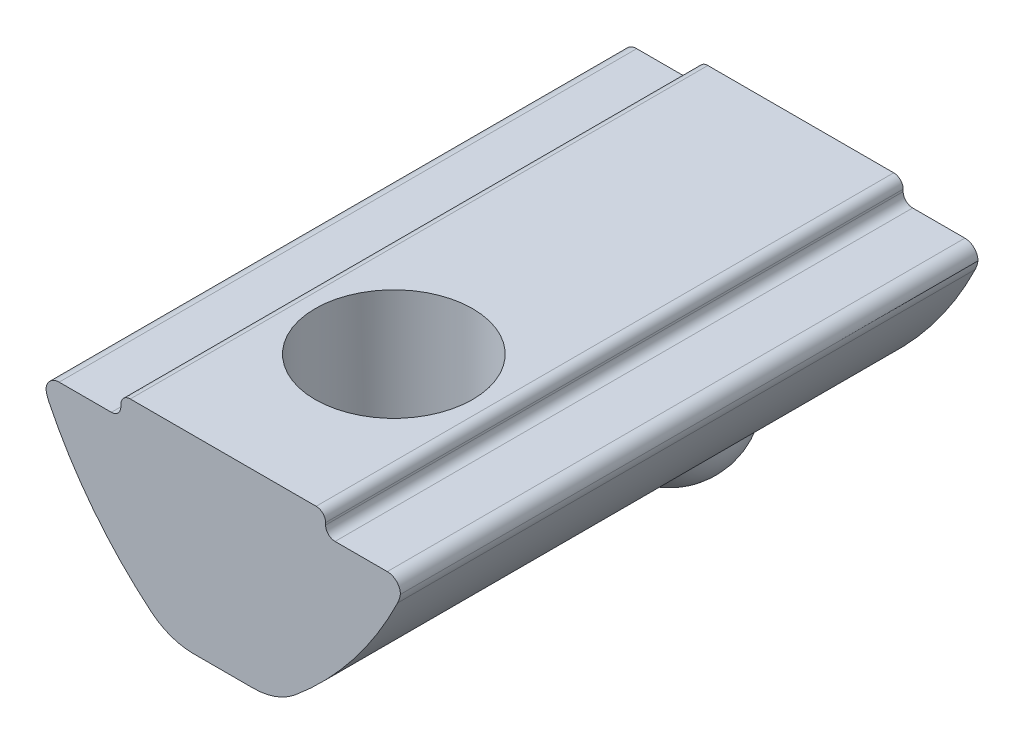
SolidWorks part; units mm, degrees
material "Plain Carbon Steel"
ref_plane "Front Plane" through (0, 0, 0) normal (0, 0, 1) x (1, 0, 0)
ref_plane "Top Plane" through (0, 0, 0) normal (0, 1, 0) x (1, 0, 0)
ref_plane "Right Plane" through (0, 0, 0) normal (1, 0, 0) x (0, 0, -1)
sketch "Sketch1" plane through (0, 0, 0) normal (0, 1, 0) x (1, 0, 0)
  circle A0 centre (0, 0) radius 3
  point P2 (3, 0)
  point P3 (-3, 0)
  dimension "D1" = 6
extrude "Boss-Extrude1" add sketch "Sketch1" against normal blind 16
sketch "Sketch2" plane through (0, -16, 0) normal (0, -1, 0) x (1, 0, 0)
  circle A1 centre (0, 0) radius 3
  circle A2 centre (0, 0) radius 3
  point P0 (0, -3)
  dimension "D1" = 0
curve "Helix/Spiral1" pitch 1 height 17 turns 17
sketch "Sketch3" plane through (0, 0, 0) normal (1, 0, 0) x (0, 0, -1)
  line L0 (3.1083, -15.9375) -> (2.2422, -16.4375) construction
  line L1 (2.2422, -16.4375) -> (3.1083, -16.9375) construction
  line L2 (3.1083, -16.9375) -> (3.1083, -15.9375) construction
  line L3 (2.3505, -16.375) -> (2.3505, -16.5) construction
  line L4 (3, -16) -> (3, -16.875) construction
  line L5 (2.2422, -16.4375) -> (2.3505, -16.4375) construction
  line L6 (3, -16.4375) -> (3.1083, -16.4375) construction
  line L8 (2.2422, -16.4375) -> (-3, -16.4375) construction
  line L9 (2.3505, -16.375) -> (3.0541, -15.9688)
  line L10 (2.3505, -16.375) -> (2.3505, -16.5)
  line L11 (2.3505, -16.5) -> (3.0541, -16.9063)
  line L12 (3.0541, -16.9063) -> (3.0541, -15.9688)
  line L14 (-3, -16.4375) -> (-3, -15.4375) construction
  line L15 (-3, -15.4375) -> (-3, -14.4375) construction
  line L16 (-3, -14.4375) -> (-3, -13.4375) construction
  line L17 (-3, -13.4375) -> (-3, -12.4375) construction
  line L18 (-3, 0) -> (-3, -16) construction
  point P15 (3.0541, -16.4375)
  dimension "D1" = 1
  dimension "D2" = 0.125
sweep "Cut-Sweep1" cut profiles "Sketch3" path "Helix/Spiral1" align with end faces yes
sketch "SketchZ" plane through (0, 0, 0) normal (0, 0, 1) x (1, 0, 0)
  line L0 (0, -16.4375) -> (0, -15.9375) construction
  line L1 (0, -16.1875) -> (3, -16.1875) construction
  line L2 (3, -16.1875) -> (3, -15.1875) construction
  line L3 (0, -16.4375) -> (0, -15.4375) construction
sketch "Sketch4" plane through (0, -16, 0) normal (0, -1, 0) x (1, 0, 0)
  circle A0 centre (0, 0) radius 2.2422
extrude "Cut-Extrude1" cut sketch "Sketch4" against normal blind 1 draft 45 flip side to cut
sketch "Sketch5" plane through (0, 0, 0) normal (0, 0, 1) x (1, 0, 0)
  line L0 (0, 3.3) -> (0, 0)
  line L1 (0, 0) -> (-6.8, 0) construction
  line L2 (0, 3.3) -> (-3, 3.3)
  line L3 (-6.8, 0) -> (-6.8, 0.825) construction
  line L4 (-6.8, 0.825) -> (-5.25, 0.825) construction
  line L5 (0, 0) -> (0, -13.9857) construction
  line L6 (-5.25, 0.825) -> (-5.25, 0)
  line L7 (-5.25, 0) -> (0, 0)
  arc A0 (-5.25, 0.825) -> (-3, 3.3) centre (0, -1.6875) cw
  dimension "D1" = 10.5
  dimension "D2" = 6.8
  dimension "D3" = 3.3
  dimension "D4" = 0.825
revolve "Revolve1" add sketch "Sketch5" angle 360 mid plane about L5
sketch "Sketch6" plane through (0, 3.3, 0) normal (0, 1, 0) x (1, 0, 0)
  line L1 (0, 2.3094) -> (-2, 1.1547)
  line L2 (-2, 1.1547) -> (-2, -1.1547)
  line L3 (-2, -1.1547) -> (0, -2.3094)
  line L4 (0, -2.3094) -> (2, -1.1547)
  line L5 (2, -1.1547) -> (2, 1.1547)
  line L6 (2, 1.1547) -> (0, 2.3094)
  circle A0 centre (0, 0) radius 2 construction
  dimension "D1" = 4
extrude "Cut-Extrude2" cut sketch "Sketch6" against normal blind 2.4
sketch "Sketch7" plane through (0, 3.3, 0) normal (0, 1, 0) x (1, 0, 0)
  circle A0 centre (0, 0) radius 2.3094
extrude "Cut-Extrude3" cut sketch "Sketch7" against normal blind 2.4 draft 45
sketch "Sketch8" plane through (0, 0, 0) normal (0, 0, 1) x (1, 0, 0)
  line L0 (6.75, -8) -> (6.75, -15.2) construction
  line L4 (6.75, -15.2) -> (-6.75, -15.2) construction
  line L7 (-6.75, -8) -> (6.75, -8) construction
  line L10 (0, 0) -> (0, -8) construction
  line L11 (-6.75, -15.2) -> (-6.75, -8) construction
  line L12 (-1.1419, -15.2) -> (1.1419, -15.2)
  line L13 (-3.54, -8) -> (3.54, -8)
  line L14 (-3.9, -8.36) -> (-3.9, -8.44)
  line L15 (-4.26, -8.8) -> (-6.25, -8.8)
  line L16 (3.9, -8.36) -> (3.9, -8.44)
  line L17 (4.26, -8.8) -> (6.25, -8.8)
  line L18 (0, -8) -> (0, -15.2) construction
  arc A1 (-2.741, -14.6217) -> (-6.6417, -9.6394) centre (6.8537, -3.0916) cw
  arc A2 (-3.54, -8) -> (-3.9, -8.36) centre (-3.54, -8.36) ccw
  arc A3 (-3.9, -8.44) -> (-4.26, -8.8) centre (-4.26, -8.44) cw
  arc A4 (-6.25, -8.8) -> (-6.75, -9.3) centre (-6.25, -9.3) ccw
  arc A5 (-6.75, -9.3) -> (-6.6417, -9.6394) centre (-5.5171, -9.0938) ccw
  arc A6 (-1.1419, -15.2) -> (-2.741, -14.6217) centre (-1.1419, -12.7) cw
  arc A7 (3.54, -8) -> (3.9, -8.36) centre (3.54, -8.36) cw
  arc A8 (3.9, -8.44) -> (4.26, -8.8) centre (4.26, -8.44) ccw
  arc A9 (6.25, -8.8) -> (6.75, -9.3) centre (6.25, -9.3) cw
  arc A10 (6.75, -9.3) -> (6.6417, -9.6394) centre (5.5171, -9.0938) cw
  arc A11 (2.741, -14.6217) -> (6.6417, -9.6394) centre (-6.8537, -3.0916) ccw
  arc A12 (1.1419, -15.2) -> (2.741, -14.6217) centre (1.1419, -12.7) ccw
  point P4 (-2, -15.2)
  point P25 (-2, -15.2)
  dimension "D1" = 13.5
  dimension "D3" = 4
  dimension "D4" = 15
  dimension "D6" = 7.8
  dimension "D8" = 0.36
  dimension "D9" = 1.25
  dimension "D10" = 0.5
  dimension "D11" = 2.5
  dimension "D2" = 8
  dimension "D5" = 7.2
  dimension "D7" = 0.8
extrude "Boss-Extrude2" add sketch "Sketch8" against normal blind 22 from offset 6.5 separate body
sketch "Sketch9" plane through (0, 0, 0) normal (0, 1, 0) x (1, 0, 0)
  line L0 (0, -6.5) -> (0, 0) construction
  line L1 (0, 0) -> (0, 10.5) construction
  line L3 (3.54, -6.5) -> (-3.54, -6.5) construction
  circle A1 centre (0, 10.5) radius 2.5 construction
  circle A2 centre (0, 0) radius 3
  circle A3 centre (0, 0) radius 3
  point P9 (0, 13)
  dimension "D3" = 5
  dimension "D1" = 17
  dimension "D2" = 0
extrude "Cut-Extrude4" cut sketch "Sketch9" against normal through all
sketch "Sketch10" plane through (0, 0, 0) normal (1, 0, 0) x (0, 0, -1)
  line L1 (10.5, -9.2) -> (13, -9.2)
  line L2 (10.5, -9.2) -> (10.5, -15.2)
  line L3 (10.5, -15.2) -> (13, -15.2)
  line L4 (13, -9.2) -> (13, -15.2)
  line L5 (15.5, -15.2) -> (2.7742, -15.2) construction
  line L8 (10.5, -9.2) -> (10.5, 0) construction
  dimension "D1" = 6
revolve "Cut-Revolve1" cut sketch "Sketch10" angle 360 about L8
sketch "Sketch11" plane through (0, 0, 0) normal (1, 0, 0) x (0, 0, -1)
  line L0 (10.5, -9.2) -> (10.5, -15.2) construction
  line L1 (13, -9.2) -> (13, -15.2) construction
  line L2 (10.5, -12.1) -> (10.5, -17.1)
  line L4 (15.5, -8) -> (-6.5, -8) construction
  arc A0 (10.5, -17.1) -> (10.5, -12.1) centre (10.5, -14.6) ccw
  dimension "D1" = 9.1
revolve "Revolve2" add sketch "Sketch11" angle 360 about L2
delete or keep bodies "Body-Delete/Keep 1" type delete bodies bodies 110
equation "\"D3@Helix/Spiral1\" = \"D4@Helix/Spiral1\" + \"D1@Boss-Extrude1\""
equation "\"D1@Sketch3\" = \"D4@Helix/Spiral1\""
equation "\"D2@Sketch3\" = \"D1@Sketch3\" / 8"
equation "\"D1@Cut-Extrude1\" = \"D4@Helix/Spiral1\""
equation "\"D1@Cut-Extrude2\" = \"D1@Sketch6\" * 3/5"
equation "\"D1@Cut-Extrude3\" = \"D1@Cut-Extrude2\""
equation "\"D4@Sketch5\" = \"D3@Sketch5\" * 1/4"
